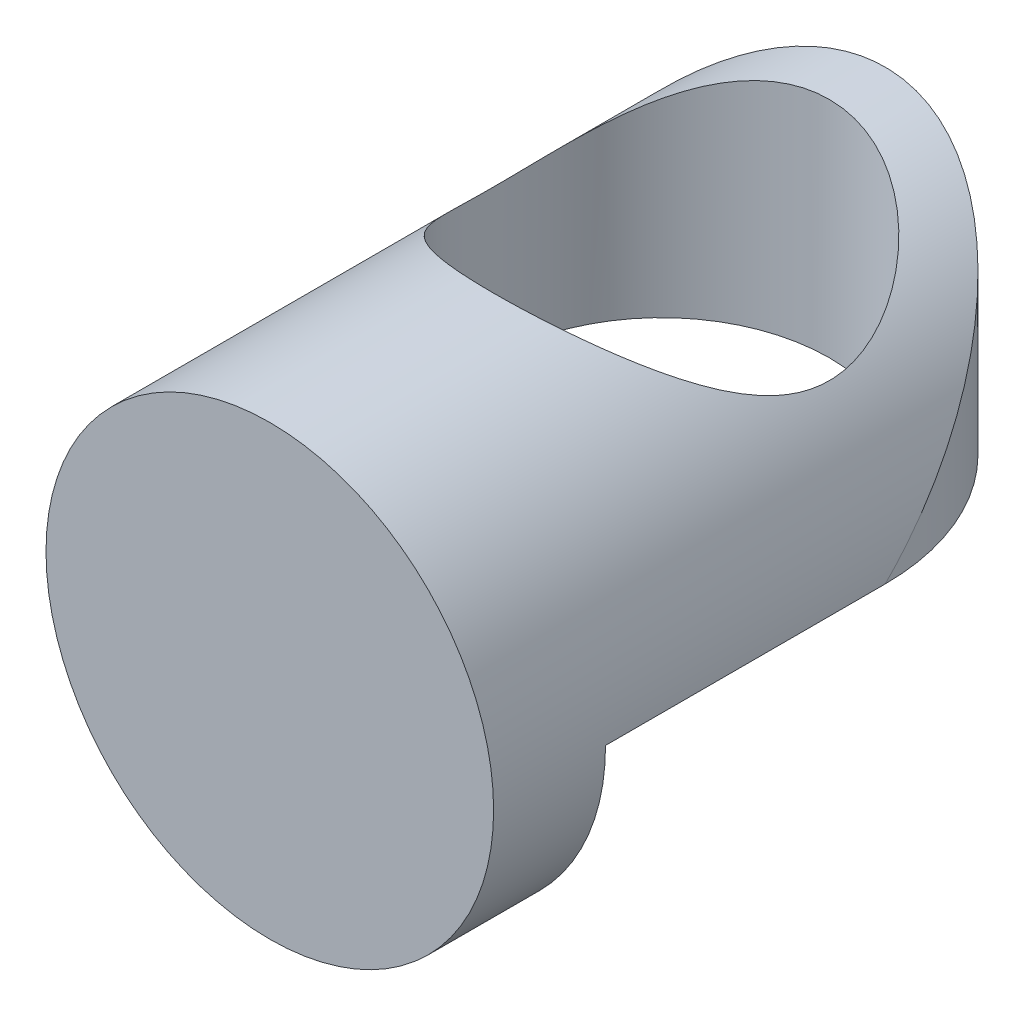
SolidWorks part; units mm, degrees
ref_plane "Front Plane" through (0, 0, 0) normal (0, 0, 1) x (1, 0, 0)
ref_plane "Top Plane" through (0, 0, 0) normal (0, 1, 0) x (1, 0, 0)
ref_plane "Right Plane" through (0, 0, 0) normal (1, 0, 0) x (0, 0, -1)
sketch "Sketch1" plane through (0, 0, 0) normal (0, 0, 1) x (1, 0, 0)
  circle A0 centre (0, 0) radius 25.4
  dimension "D1" = 50.8
extrude "Boss-Extrude1" add sketch "Sketch1" along normal blind 12.7
sketch "Sketch2" plane through (0, 0, 0) normal (0, 1, 0) x (1, 0, 0)
  line L0 (25.4, -12.7) -> (25.4, 0) construction
  line L1 (-25.4, 0) -> (25.4, 0)
  line L2 (-25.4, 0) -> (-25.4, 31.75)
  line L3 (-25.4, 31.75) -> (25.4, 31.75)
  line L4 (25.4, 0) -> (25.4, 31.75)
  circle A0 centre (0, 31.75) radius 25.4
  dimension "D1" = 31.75
extrude "Boss-Extrude2" add sketch "Sketch2" along normal blind 25.4 contours A0 | L2 L1 L4 L3
sketch "Sketch3" plane through (0, 0, 0) normal (0, 0, 1) x (1, 0, 0)
  line L0 (25.4, 0) -> (25.4, 25.4) construction
  line L1 (25.4, 25.4) -> (0, 25.4) construction
  line L2 (0, 25.4) -> (-25.4, 25.4) construction
  line L3 (-25.4, 25.4) -> (-25.4, 0) construction
  line L4 (25.4, 0) -> (25.4, 25.4)
  line L5 (25.4, 25.4) -> (0, 25.4)
  line L6 (0, 25.4) -> (-25.4, 25.4)
  line L7 (-25.4, 25.4) -> (-25.4, 0)
  arc A0 (25.4, 0) -> (0, 25.4) centre (0, 0) ccw construction
  arc A1 (0, 25.4) -> (-25.4, 0) centre (0, 0) ccw construction
  arc A2 (25.4, 0) -> (0, 25.4) centre (0, 0) ccw
  arc A3 (0, 25.4) -> (-25.4, 0) centre (0, 0) ccw
extrude "Cut-Extrude1" cut sketch "Sketch3" against normal through all contours L5 L4 A2 | A3 L7 L6
sketch "Sketch4" plane through (0, 0, 0) normal (0, -1, 0) x (1, 0, 0)
  circle A0 centre (0, -31.75) radius 19.05
  arc A1 (-25.4, -31.75) -> (25.4, -31.75) centre (0, -31.75) ccw construction
  dimension "D1" = 38.1
extrude "Cut-Extrude2" cut sketch "Sketch4" against normal through all
